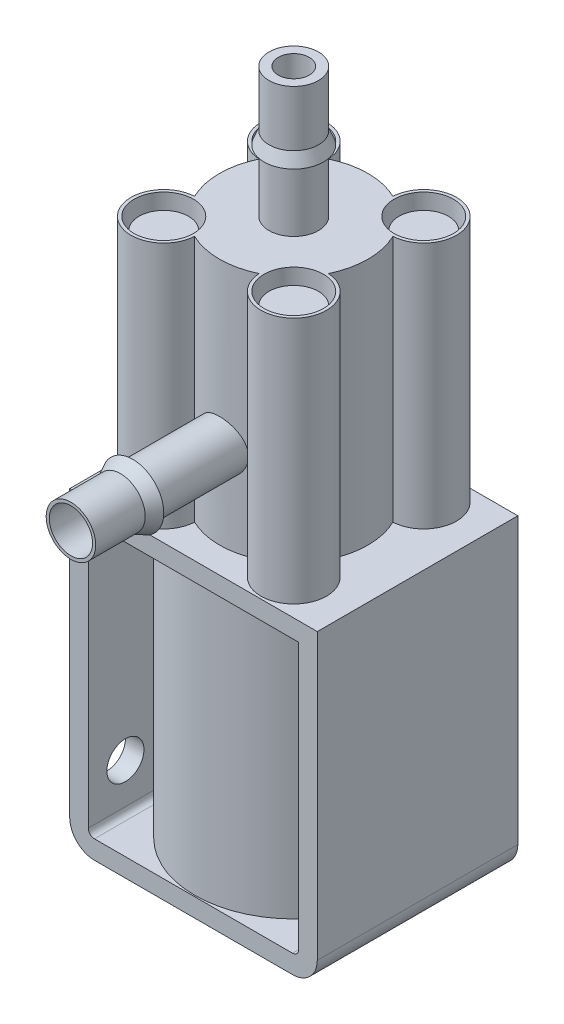
SolidWorks part; units mm, degrees
ref_plane "Front Plane" through (0, 0, 0) normal (0, 0, 1) x (1, 0, 0)
ref_plane "Top Plane" through (0, 0, 0) normal (0, 1, 0) x (1, 0, 0)
ref_plane "Right Plane" through (0, 0, 0) normal (1, 0, 0) x (0, 0, -1)
sketch "Sketch1" plane through (0, 0, 0) normal (0, 0, 1) x (1, 0, 0)
  line L0 (-8.5, 11) -> (-8.5, -10.5)
  line L1 (-10, 12.5) -> (10, 12.5)
  line L2 (-10, 12.5) -> (-10, -10.5)
  line L3 (-8, -12.5) -> (8, -12.5)
  line L4 (10, 12.5) -> (10, -10.5)
  line L5 (-10, 12.5) -> (10, -12.5) construction
  line L6 (-10, -12.5) -> (10, 12.5) construction
  line L7 (-8, -11) -> (8, -11)
  line L8 (8.5, 11) -> (8.5, -10.5)
  line L9 (-8.5, 11) -> (8.5, 11)
  arc A0 (8, -12.5) -> (10, -10.5) centre (8, -10.5) ccw
  arc A1 (-10, -10.5) -> (-8, -12.5) centre (-8, -10.5) ccw
  arc A2 (-8.5, -10.5) -> (-8, -11) centre (-8, -10.5) ccw
  arc A3 (8, -11) -> (8.5, -10.5) centre (8, -10.5) ccw
  point P0 (0, 0)
  dimension "D3" = 2
  dimension "D1" = 25
  dimension "D2" = 20
  dimension "D4" = 1.5
extrude "Boss-Extrude1" add sketch "Sketch1" along normal blind 8.1 and the other way blind 8.1
sketch "Sketch2" plane through (0, -11, 0) normal (0, 1, 0) x (1, 0, 0)
  circle A0 centre (0, 0) radius 8
  dimension "D1" = 16
extrude "Boss-Extrude5" add sketch "Sketch2" along normal up to next
sketch "Sketch3" plane through (0, -12.5, 0) normal (0, -1, 0) x (1, 0, 0)
  circle A0 centre (0, 0) radius 2.5
  dimension "D1" = 5
extrude "Boss-Extrude6" add sketch "Sketch3" along normal blind 0.5
sketch "Sketch4" plane through (0, 12.5, 0) normal (0, 1, 0) x (1, 0, 0)
  line L1 (-5.25, -5.25) -> (5.25, -5.25) construction
  line L2 (-5.25, -5.25) -> (-5.25, 5.25) construction
  line L3 (-5.25, 5.25) -> (5.25, 5.25) construction
  line L4 (5.25, -5.25) -> (5.25, 5.25) construction
  line L5 (-5.25, -5.25) -> (5.25, 5.25) construction
  line L6 (-5.25, 5.25) -> (5.25, -5.25) construction
  arc A0 (-5.4052, 2.6045) -> (-5.4052, -2.6045) centre (0, 0) ccw
  arc A1 (5.4052, 2.6045) -> (2.6045, 5.4052) centre (5.25, 5.25) ccw
  arc A2 (2.6045, -5.4052) -> (5.4052, -2.6045) centre (5.25, -5.25) ccw
  arc A3 (-5.4052, -2.6045) -> (-2.6045, -5.4052) centre (-5.25, -5.25) ccw
  arc A4 (-2.6045, 5.4052) -> (-5.4052, 2.6045) centre (-5.25, 5.25) ccw
  arc A5 (2.6045, 5.4052) -> (-2.6045, 5.4052) centre (0, 0) ccw
  arc A6 (5.4052, -2.6045) -> (5.4052, 2.6045) centre (0, 0) ccw
  arc A7 (-2.6045, -5.4052) -> (2.6045, -5.4052) centre (0, 0) ccw
  circle A8 centre (-5.25, 5.25) radius 2.4
  circle A9 centre (5.25, 5.25) radius 2.4
  circle A10 centre (5.25, -5.25) radius 2.4
  circle A11 centre (-5.25, -5.25) radius 2.4
  circle A12 centre (-5.25, -5.25) radius 2.65 construction
  circle A13 centre (5.25, -5.25) radius 2.65 construction
  circle A14 centre (5.25, 5.25) radius 2.65 construction
  circle A15 centre (-5.25, 5.25) radius 2.65 construction
  dimension "D1" = 12
  dimension "D2" = 15.8
  dimension "D3" = 5.3
  dimension "D4" = 0.25
extrude "Boss-Extrude7" add sketch "Sketch4" along normal blind 20
sketch "Sketch6" plane through (0, 0, 0) normal (0, 0, 1) x (1, 0, 0)
  line L0 (0, 32.5) -> (0, 43) construction
  line L1 (2.6045, 32.5) -> (-2.6045, 32.5) construction
  line L2 (1.25, 32.5) -> (1.25, 43)
  line L3 (1.25, 43) -> (2, 43)
  line L4 (2, 43) -> (2, 38.5)
  line L5 (2, 38.5) -> (2.4, 37.5)
  line L6 (2.4, 37.5) -> (2, 37.5)
  line L7 (2, 37.5) -> (2, 32.5)
  line L8 (7.9, 32.5) -> (2.6045, 32.5) construction
  line L9 (2, 32.5) -> (1.25, 32.5)
  dimension "D1" = 4
  dimension "D2" = 0.75
  dimension "D3" = 10.5
  dimension "D4" = 4.8
  dimension "D5" = 5
  dimension "D6" = 1
revolve "Revolve1" add sketch "Sketch6" angle 360 about L0
sketch "Sketch8" plane through (0, 12.5, 0) normal (0, 1, 0) x (1, 0, 0)
  circle A0 centre (-5.25, 5.25) radius 2
  circle A1 centre (5.25, 5.25) radius 2
  circle A2 centre (5.25, -5.25) radius 2
  circle A3 centre (-5.25, -5.25) radius 2
  dimension "D1" = 4
extrude "Boss-Extrude8" add sketch "Sketch8" along normal blind 19
sketch "Sketch11" plane through (0, 0, 0) normal (0, 0, 1) x (1, 0, 0)
  line L2 (10, 12.5) -> (-10, 12.5) construction
  circle A0 centre (0, 19.5) radius 2
  circle A1 centre (0, 19.5) radius 1.75
  dimension "D1" = 4
  dimension "D2" = 3.5
  dimension "D3" = 5
extrude "Boss-Extrude10" add sketch "Sketch11" along normal blind 18
sketch "Sketch12" plane through (0, 0, 0) normal (1, 0, 0) x (0, 0, -1)
  line L0 (-14, 21.5) -> (-13, 22)
  line L1 (-6, 21.5) -> (-18, 21.5) construction
  line L2 (-13, 22) -> (-13, 21.5)
  line L3 (-13, 21.5) -> (-14, 21.5)
  dimension "D1" = 1
  dimension "D2" = 0.5
  dimension "D3" = 4
revolve "Revolve2" add sketch "Sketch12" angle 360 about axis through (0, 19.5, 18) along (0, 0, -1)
sketch "Sketch13" plane through (-10, 0, 0) normal (-1, 0, 0) x (0, 0, 1)
  line L2 (-8.1, 12.5) -> (-8.1, -10.5) construction
  line L3 (-5.1, 7.25) -> (0, 7.25) construction
  line L4 (5.1, -7.25) -> (0, -7.25) construction
  line L5 (0, -7.25) -> (0, 7.25) construction
  circle A0 centre (-5.1, 7.25) radius 1.5
  circle A1 centre (5.1, -7.25) radius 1.5
  point P9 (0, 0)
  dimension "D1" = 3
  dimension "D2" = 1.5
  dimension "D3" = 14.5
extrude "Cut-Extrude1" cut sketch "Sketch13" against normal up to next
